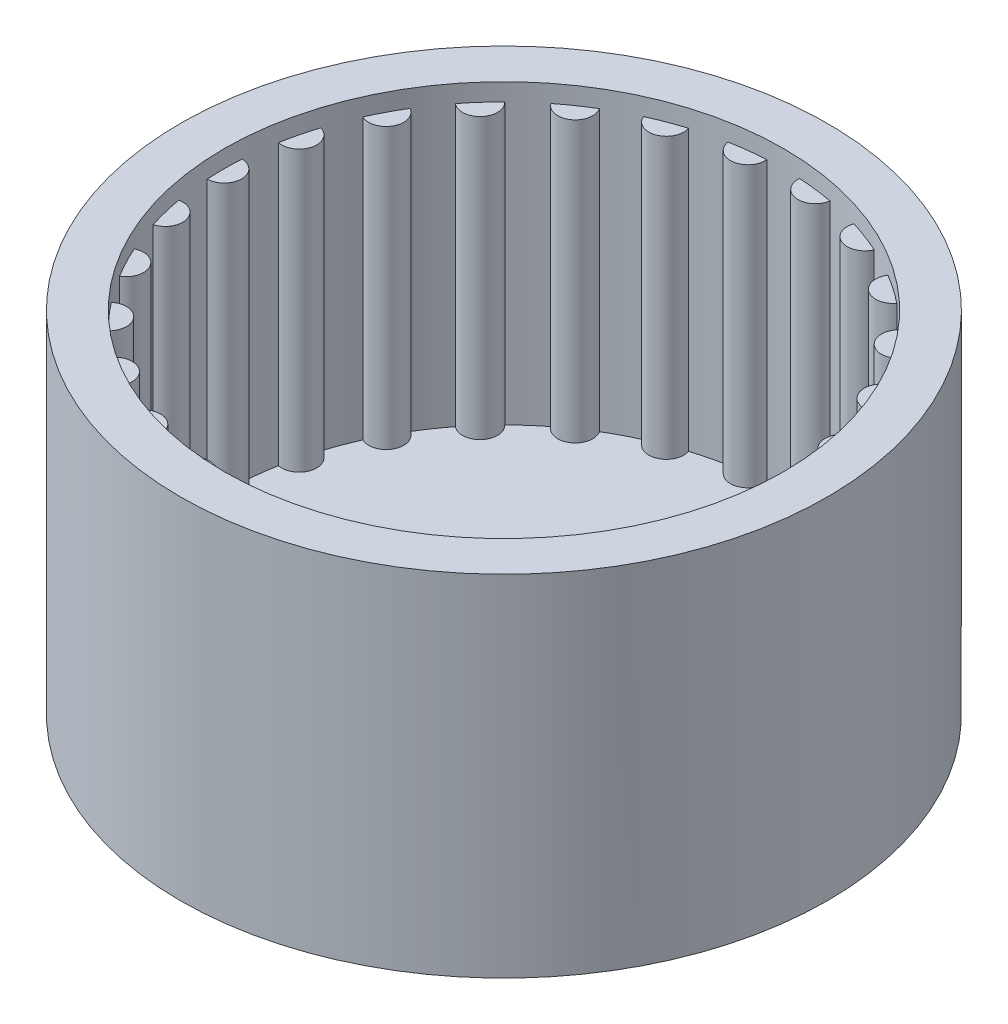
SolidWorks part; units mm, degrees
ref_plane "Front Plane" through (0, 0, 0) normal (0, 0, 1) x (1, 0, 0)
ref_plane "Top Plane" through (0, 0, 0) normal (0, 1, 0) x (1, 0, 0)
ref_plane "Right Plane" through (0, 0, 0) normal (1, 0, 0) x (0, 0, -1)
sketch "Sketch1" plane through (0, 0, 0) normal (0, 1, 0) x (1, 0, 0)
  circle A0 centre (15.5, 0) radius 1
  circle A1 centre (15.0351, -3.8291) radius 1
  circle A2 centre (13.6673, -7.4356) radius 1
  circle A3 centre (11.4762, -10.61) radius 1
  circle A4 centre (8.589, -13.1677) radius 1
  circle A5 centre (5.1737, -14.9603) radius 1
  circle A6 centre (1.4286, -15.8833) radius 1
  circle A7 centre (-2.4286, -15.8833) radius 1
  circle A8 centre (-6.1737, -14.9603) radius 1
  circle A9 centre (-9.589, -13.1677) radius 1
  circle A10 centre (-12.4762, -10.61) radius 1
  circle A11 centre (-14.6673, -7.4356) radius 1
  circle A12 centre (-16.0351, -3.8291) radius 1
  circle A13 centre (-16.5, 0) radius 1
  circle A14 centre (-16.0351, 3.8291) radius 1
  circle A15 centre (-14.6673, 7.4356) radius 1
  circle A16 centre (-12.4762, 10.61) radius 1
  circle A17 centre (-9.589, 13.1677) radius 1
  circle A18 centre (-6.1737, 14.9603) radius 1
  circle A19 centre (-2.4286, 15.8833) radius 1
  circle A20 centre (1.4286, 15.8833) radius 1
  circle A21 centre (5.1737, 14.9603) radius 1
  circle A22 centre (8.589, 13.1677) radius 1
  circle A23 centre (11.4762, 10.61) radius 1
  circle A24 centre (13.6673, 7.4356) radius 1
  circle A25 centre (15.0351, 3.8291) radius 1
  spline S0 degree 4 number of poles 315 (14.4, 0) -> (-15.4, 0) construction
sketch "Sketch2" plane through (0, 0, 0) normal (0, 1, 0) x (1, 0, 0)
  circle A0 centre (15.5, 0) radius 1
  circle A1 centre (15.0351, -3.8291) radius 1
  circle A2 centre (13.6673, -7.4356) radius 1
  circle A3 centre (11.4762, -10.61) radius 1
  circle A4 centre (8.589, -13.1677) radius 1
  circle A5 centre (5.1737, -14.9603) radius 1
  circle A6 centre (1.4286, -15.8833) radius 1
  circle A7 centre (-2.4286, -15.8833) radius 1
  circle A8 centre (-6.1737, -14.9603) radius 1
  circle A9 centre (-9.589, -13.1677) radius 1
  circle A10 centre (-12.4762, -10.61) radius 1
  circle A11 centre (-14.6673, -7.4356) radius 1
  circle A12 centre (-16.0351, -3.8291) radius 1
  circle A13 centre (-16.5, 0) radius 1
  circle A14 centre (-16.0351, 3.8291) radius 1
  circle A15 centre (-14.6673, 7.4356) radius 1
  circle A16 centre (-12.4762, 10.61) radius 1
  circle A17 centre (-9.589, 13.1677) radius 1
  circle A18 centre (-6.1737, 14.9603) radius 1
  circle A19 centre (-2.4286, 15.8833) radius 1
  circle A20 centre (1.4286, 15.8833) radius 1
  circle A21 centre (5.1737, 14.9603) radius 1
  circle A22 centre (8.589, 13.1677) radius 1
  circle A23 centre (11.4762, 10.61) radius 1
  circle A24 centre (13.6673, 7.4356) radius 1
  circle A25 centre (15.0351, 3.8291) radius 1
extrude "Boss-Extrude1" add sketch "Sketch2" along normal blind 8 and the other way blind 8
sketch "Sketch4" plane through (0, 0, 0) normal (0, 1, 0) x (1, 0, 0)
  line L0 (-15.4, 0) -> (14.4, 0) construction
  line L1 (0, 0) -> (0, 14.9128) construction
  line L2 (0, 0) -> (0, -14.9128) construction
  line L3 (0, 0) -> (-0.5, 0) construction
  line L4 (-0.5, 0) -> (-0.5, 15.3103) construction
  line L5 (-0.5, 0) -> (-0.5, -15.3103) construction
  line L6 (14.4, 0) -> (15.5, 0) construction
  line L7 (0, 0) -> (10, 0) construction
  line L8 (7.9, 0) -> (9.5, 0)
  line L9 (-0.5, 0) -> (9.5, 0) construction
  line L10 (-0.5, 15.3103) -> (-0.5, -15.3103) construction
  circle A0 centre (-0.5, 0) radius 16
  circle A1 centre (15.5, 0) radius 1
  circle A2 centre (15.0351, -3.8291) radius 1
  circle A3 centre (13.6673, -7.4356) radius 1
  circle A4 centre (11.4762, -10.61) radius 1
  circle A5 centre (8.589, -13.1677) radius 1
  circle A6 centre (5.1737, -14.9603) radius 1
  circle A7 centre (1.4286, -15.8833) radius 1
  circle A8 centre (-2.4286, -15.8833) radius 1
  circle A9 centre (-6.1737, -14.9603) radius 1
  circle A10 centre (-9.589, -13.1677) radius 1
  circle A11 centre (-12.4762, -10.61) radius 1
  circle A12 centre (-14.6673, -7.4356) radius 1
  circle A13 centre (-16.0351, -3.8291) radius 1
  circle A14 centre (-16.5, 0) radius 1
  circle A15 centre (-16.0351, 3.8291) radius 1
  circle A16 centre (-14.6673, 7.4356) radius 1
  circle A17 centre (-12.4762, 10.61) radius 1
  circle A18 centre (-9.589, 13.1677) radius 1
  circle A19 centre (-6.1737, 14.9603) radius 1
  circle A20 centre (-2.4286, 15.8833) radius 1
  circle A21 centre (1.4286, 15.8833) radius 1
  circle A22 centre (5.1737, 14.9603) radius 1
  circle A23 centre (8.589, 13.1677) radius 1
  circle A24 centre (11.4762, 10.61) radius 1
  circle A25 centre (13.6673, 7.4356) radius 1
  circle A26 centre (15.0351, 3.8291) radius 1
  circle A27 centre (0, 0) radius 10
  circle A28 centre (10, 0) radius 2.1
  circle A29 centre (5, -8.6603) radius 2.1
  circle A30 centre (-5, -8.6603) radius 2.1
  circle A31 centre (-10, 0) radius 2.1
  circle A32 centre (-5, 8.6603) radius 2.1
  circle A33 centre (5, 8.6603) radius 2.1
  circle A34 centre (-6, 8.6603) radius 2.1
  circle A35 centre (4, 8.6603) radius 2.1
  circle A36 centre (9, 0) radius 2.1
  circle A37 centre (4, -8.6603) radius 2.1
  circle A38 centre (-6, -8.6603) radius 2.1
  circle A39 centre (-1, 0) radius 10
  circle A40 centre (-11, 0) radius 2.1
  circle A41 centre (9.5, 0) radius 1.5
  circle A42 centre (4.5, -8.6603) radius 1.5
  circle A43 centre (-5.5, -8.6603) radius 1.5
  circle A44 centre (-10.5, 0) radius 1.5
  circle A45 centre (-5.5, 8.6603) radius 1.5
  circle A46 centre (4.5, 8.6603) radius 1.5
  circle A47 centre (-0.5, 0) radius 19.5
  circle A48 centre (0, 0) radius 5.55
  circle A49 centre (-0.5, 0) radius 5.55
  spline S0 degree 4 number of poles 369 (14.1521, 3.1658) -> (-14.9531, 3.4358) construction
  spline S1 degree 4 number of poles 315 (14.4, 0) -> (-15.4, 0)
  spline S2 degree 4 number of poles 315 (14.4, 0) -> (-15.4, 0)
  spline S3 degree 4 number of poles 315 (-15.4, 0) -> (14.4, 0)
  spline S4 degree 4 number of poles 315 (-15.4, 0) -> (14.4, 0)
  dimension "D1" = 32
  dimension "D2" = 2
  dimension "D4" = 20
  dimension "D5" = 4.2
  dimension "D8" = 6
  dimension "D7" = 10
  dimension "D9" = 10
  dimension "D3" = 26
  dimension "D6" = 6
sketch "Sketch5" plane through (0, 0, 0) normal (0, 1, 0) x (1, 0, 0)
  circle A0 centre (-0.5, 0) radius 16
  circle A1 centre (-0.5, 0) radius 18.5
extrude "Boss-Extrude3" add sketch "Sketch5" along normal blind 8 and the other way blind 8
sketch "Sketch6" plane through (0, 8, 0) normal (0, 1, 0) x (1, 0, 0)
  circle A0 centre (-0.5, 0) radius 18.5 construction
  circle A1 centre (-0.5, 0) radius 18.5
  circle A2 centre (-0.5, 0) radius 16
  dimension "D1" = 37
  dimension "D2" = 32
extrude "Boss-Extrude4" add sketch "Sketch6" along normal blind 1
sketch "Sketch7" plane through (0, 9, 0) normal (0, 1, 0) x (1, 0, 0)
  circle A0 centre (-0.5, 0) radius 18.5 construction
  circle A1 centre (-5.5, -8.6603) radius 1.5 construction
  circle A2 centre (4.5, -8.6603) radius 1.5 construction
  circle A3 centre (9.5, 0) radius 1.5 construction
  circle A4 centre (-10.5, 0) radius 1.5 construction
  circle A5 centre (-5.5, 8.6603) radius 1.5 construction
  circle A6 centre (4.5, 8.6603) radius 1.5 construction
  circle A7 centre (-0.5, 0) radius 18.5
  circle A8 centre (-5.5, -8.6603) radius 1.5
  circle A9 centre (4.5, -8.6603) radius 1.5
  circle A10 centre (9.5, 0) radius 1.5
  circle A11 centre (-10.5, 0) radius 1.5
  circle A12 centre (-5.5, 8.6603) radius 1.5
  circle A13 centre (4.5, 8.6603) radius 1.5
sketch "Sketch8" plane through (0, -8, 0) normal (0, -1, 0) x (1, 0, 0)
  circle A0 centre (-0.5, 0) radius 18.5
  dimension "D1" = 37
extrude "Boss-Extrude5" add sketch "Sketch8" along normal blind 3
sketch "Sketch9" plane through (0, -11, 0) normal (0, -1, 0) x (1, 0, 0)
  circle A0 centre (-0.5, 0) radius 6
  dimension "D1" = 12
extrude "Cut-Extrude1" cut sketch "Sketch9" against normal blind 3
